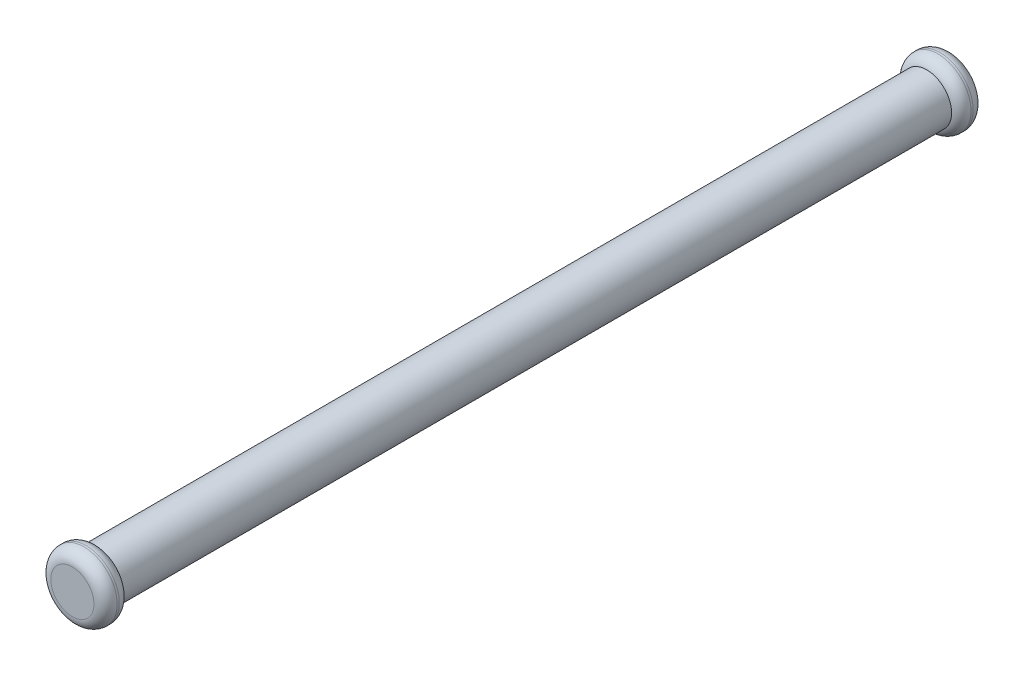
SolidWorks part; units mm, degrees
material "Aço cromo inoxidável"
ref_plane "Plano frontal" through (0, 0, 0) normal (0, 0, 1) x (1, 0, 0)
ref_plane "Plano superior" through (0, 0, 0) normal (0, 1, 0) x (1, 0, 0)
ref_plane "Plano direito" through (0, 0, 0) normal (1, 0, 0) x (0, 0, -1)
sketch "Esboço1" plane through (0, 0, 0) normal (0, 0, 1) x (1, 0, 0)
  circle A0 centre (-20, 2.5) radius 1.5
extrude "Ressalto-extrusão1" add sketch "Esboço1" against normal up to surface (50 mm away)
sketch "Esboço2" plane through (0, 0, 0) normal (0, 0, 1) x (1, 0, 0)
  circle A0 centre (-20, 2.5) radius 2
  dimension "D1" = 4
extrude "Ressalto-extrusão2" add sketch "Esboço2" along normal blind 1.5
extrude "Ressalto-extrusão3" add sketch "Esboço2<2>" against normal blind 1.5 from surface starting at face at (-21.5, 2.5, -50)
sketch "Esboço2<2>" plane through (0, 0, 0) normal (0, 0, 1) x (1, 0, 0) same geometry as "Esboço2"
fillet "Filete1" radius 0.7 4 edges at (-18, 2.5, 0) (-18, 2.5, 1.5) (-22, 2.5, -50) (-22, 2.5, -51.5)
